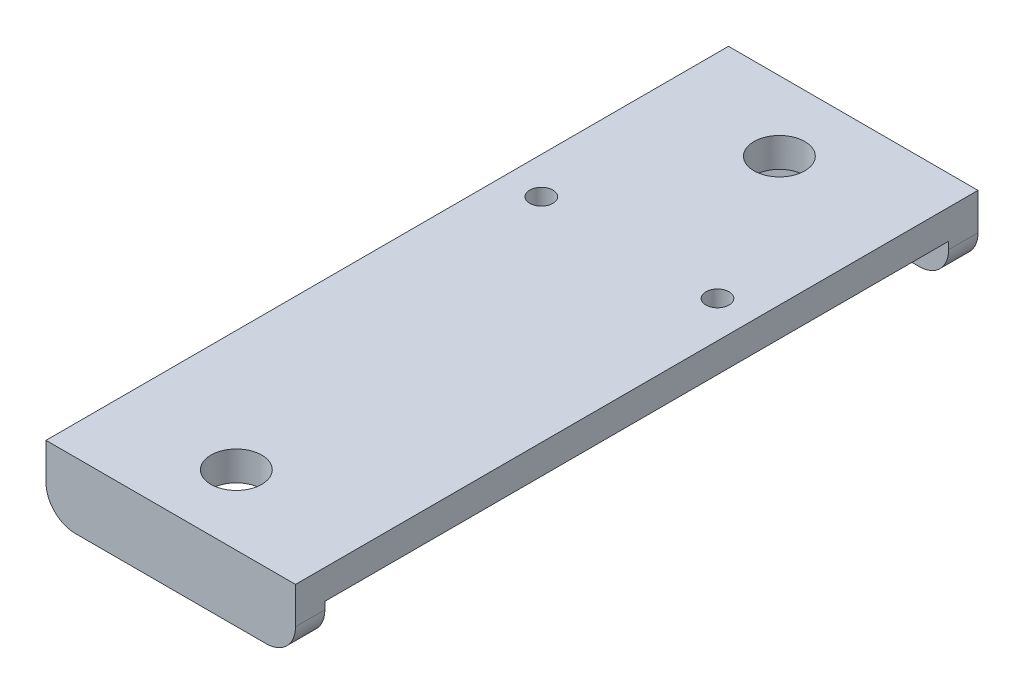
SolidWorks part; units mm, degrees
ref_plane "Front Plane" through (0, 0, 0) normal (0, 0, 1) x (1, 0, 0)
ref_plane "Top Plane" through (0, 0, 0) normal (0, 1, 0) x (1, 0, 0)
ref_plane "Right Plane" through (0, 0, 0) normal (1, 0, 0) x (0, 0, -1)
sketch "Sketch1" plane through (0, 0, 0) normal (1, 0, 0) x (0, 0, -1)
  line L0 (-26.9875, 0) -> (26.9875, 0)
  line L1 (26.9875, 0) -> (26.9875, -3.175)
  line L2 (-26.9875, 0) -> (-26.9875, -3.175)
  point P4 (0, 0)
  dimension "D1" = 53.975
  dimension "D2" = 3.175
extrude "Extrude-Thin1" add sketch "Sketch1" along normal blind 21.59 thin thin type one direction wall 2.54
sketch "Sketch2" plane through (0, 2.54, 0) normal (0, 1, 0) x (1, 0, 0)
  line L0 (0, 0) -> (21.59, 0) construction
  line L1 (21.59, 29.5275) -> (21.59, -29.5275) construction
  line L2 (10.795, -29.5275) -> (10.795, 29.5275) construction
  line L4 (21.59, -29.5275) -> (0, -29.5275) construction
  line L5 (21.59, 29.5275) -> (0, 29.5275) construction
  line L6 (3.175, 10.16) -> (18.415, 10.16) construction
  circle A2 centre (3.175, 10.16) radius 1
  circle A3 centre (18.415, 10.16) radius 1
  point P14 (10.795, 10.16)
  dimension "D1" = 15.24
  dimension "D2" = 2
  dimension "D3" = 10.16
extrude "Cut-Extrude1" cut sketch "Sketch2" against normal up to next
fillet "Fillet1" radius 2.54 4 edges at (0, -3.175, 28.2575) (21.59, -3.175, 28.2575) (0, -3.175, -28.2575) (21.59, -3.175, -28.2575)
sketch "Sketch3" plane through (0, 2.54, 0) normal (0, 1, 0) x (1, 0, 0)
  circle A0 centre (10.4368, -23.495) radius 2.2
  circle A1 centre (10.4368, 23.495) radius 2.2
extrude "Cut-Extrude2" cut sketch "Sketch3" against normal up to next
